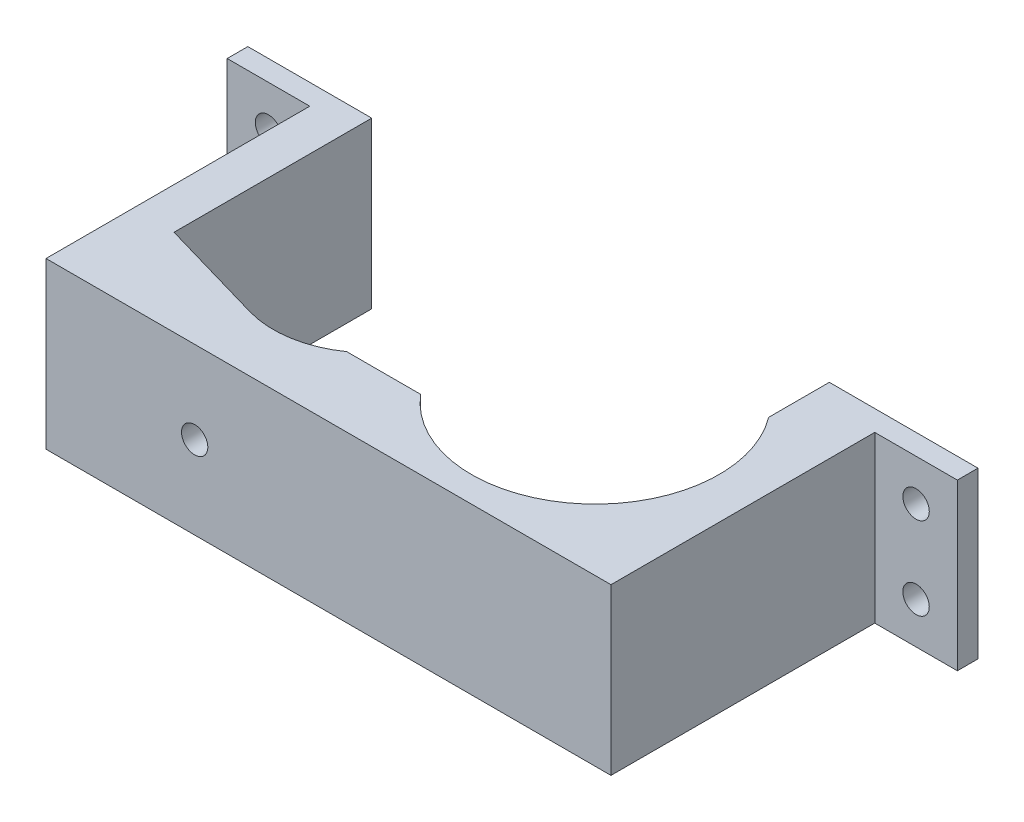
SolidWorks part; units mm, degrees
ref_plane "Front Plane" through (0, 0, 0) normal (0, 0, 1) x (1, 0, 0)
ref_plane "Top Plane" through (0, 0, 0) normal (0, 1, 0) x (1, 0, 0)
ref_plane "Right Plane" through (0, 0, 0) normal (1, 0, 0) x (0, 0, -1)
sketch "Sketch1" plane through (0, 0, 0) normal (0, 1, 0) x (1, 0, 0)
  line L0 (-20.574, -9.6521) -> (-4.162, -14.3967)
  line L1 (-4.1621, 14.3967) -> (-20.574, 9.652) construction
  line L2 (-20.574, 9.652) -> (-20.574, -9.6521)
  line L3 (-39.624, 20.7467) -> (-20.574, 20.7467)
  line L4 (-39.624, 20.7467) -> (-39.624, 17.5717)
  line L6 (49.784, 20.7467) -> (72.644, 20.7467)
  line L7 (-39.624, 17.5717) -> (-26.924, 17.5717)
  line L9 (-26.924, 17.5717) -> (-26.924, -12.8271)
  line L10 (72.644, 20.7467) -> (72.644, 17.5717)
  line L11 (72.644, 17.5717) -> (59.944, 17.5717)
  line L12 (59.944, 17.5717) -> (59.944, -12.8271)
  line L13 (-20.574, 9.652) -> (-20.574, 20.7467)
  line L15 (59.944, -12.8271) -> (59.944, -22.9871)
  line L16 (59.944, -22.9871) -> (-26.924, -22.9871)
  line L17 (-26.924, -22.9871) -> (-26.924, -12.8271)
  line L18 (53.594, 0) -> (53.594, 36.7061) construction
  line L19 (49.784, 20.7467) -> (49.784, 11.43)
  line L20 (8.5997, -12.2733) -> (19.9745, -12.2733)
  arc A0 (-4.162, -14.3967) -> (8.5997, -12.2733) centre (0, 0) ccw
  arc A1 (-26.924, -12.8271) -> (59.944, -12.8271) centre (16.51, -3.3778) ccw construction
  arc A2 (14.9527, -1.0034) -> (-4.1621, 14.3967) centre (0, 0) ccw construction
  arc A3 (8.5997, -12.2733) -> (14.9527, -1.0034) centre (0, 0) ccw construction
  arc A4 (49.784, 11.43) -> (19.9745, -12.2733) centre (34.544, 0) ccw construction
  circle A5 centre (34.544, 0) radius 19.05 construction
  arc A6 (19.9745, -12.2733) -> (49.784, 11.43) centre (34.544, 0) ccw
  point P16 (61.214, 20.7467)
  dimension "D2" = 14.9863
  dimension "D14" = 6.35
  dimension "D10" = 44.45
  dimension "D1" = 19.3041
  dimension "D3" = 16.4119
  dimension "D4" = 106.124
  dimension "D5" = 20.574
  dimension "D6" = 106.125
  dimension "D7" = 6.35
  dimension "D8" = 6.35
  dimension "D9" = 3.175
  dimension "D11" = 12.7
  dimension "D12" = 3.175
  dimension "D13" = 3.81
  dimension "D15" = 10.16
  dimension "D16" = 33.02
extrude "Boss-Extrude1" add sketch "Sketch1" along normal blind 25.4
sketch "Sketch2" plane through (0, 0, -17.5717) normal (0, 0, 1) x (1, 0, 0)
  line L0 (-39.624, 0) -> (-26.924, 0) construction
  line L1 (-39.624, 25.4) -> (-39.624, 0) construction
  line L2 (-39.624, 25.4) -> (-26.924, 25.4) construction
  line L3 (72.644, 25.4) -> (72.644, 0) construction
  circle A0 centre (-33.274, 19.05) radius 2.032
  circle A1 centre (-33.274, 6.35) radius 2.032
  circle A2 centre (66.294, 19.05) radius 2.032
  circle A3 centre (66.294, 6.35) radius 2.032
  dimension "D5" = 4.064
  dimension "D1" = 6.35
  dimension "D2" = 6.35
  dimension "D3" = 6.35
  dimension "D4" = 6.35
sketch "Sketch6" plane through (0, 0, -20.7467) normal (0, 0, -1) x (-1, 0, 0)
  line L0 (-72.644, 0) -> (-49.784, 0) construction
  line L1 (-72.644, 25.4) -> (-72.644, 0) construction
  line L2 (-72.644, 25.4) -> (-49.784, 25.4) construction
  line L4 (39.624, 25.4) -> (39.624, 0) construction
  circle A0 centre (-66.294, 6.35) radius 2.032
  circle A1 centre (-66.294, 19.05) radius 2.032
  circle A2 centre (33.274, 6.35) radius 2.032
  circle A3 centre (33.274, 19.05) radius 2.032
  dimension "D1" = 4.064
  dimension "D2" = 6.35
  dimension "D3" = 6.35
  dimension "D4" = 6.35
  dimension "D5" = 6.35
extrude "Cut-Extrude1" cut sketch "Sketch2" against normal through all
sketch "Sketch3" plane through (0, 0, 22.9871) normal (0, 0, 1) x (1, 0, 0)
  line L0 (-26.924, 25.4) -> (59.944, 25.4) construction
  line L1 (-26.924, 25.4) -> (-26.924, 0) construction
  circle A0 centre (-4.064, 12.7) radius 1.905
  dimension "D3" = 3.81
  dimension "D1" = 12.7
  dimension "D2" = 22.86
hole_wizard "#10-32 Tapped Hole1" positions "Sketch4" profile "Sketch5" tap size "#10-32" standard "ANSI Inch" end condition through all
sketch "Sketch4" plane through (0, 0, 22.9871) normal (0, 0, 1) x (1, 0, 0)
  point P0 (-4.064, 12.7)
sketch "Sketch5" plane through (-4.064, 12.7, 22.9871) normal (1, 0, 0) x (0, -1, 0)
  line L0 (0, 0) -> (0, 43.7338)
  line L1 (0, 43.7338) -> (2.0193, 43.7338)
  line L2 (2.0193, 43.7338) -> (2.0193, 0)
  line L5 (2.0193, 0) -> (0, 0)
  line L11 (0, -6.35) -> (0, 107.95) construction
  dimension "Thru Tap Drill Dia." = 4.0386
  dimension "Thru Tap Drill Depth" = 43.7338
cosmetic thread "Hole Thread1" parameters "D2"=4.826
